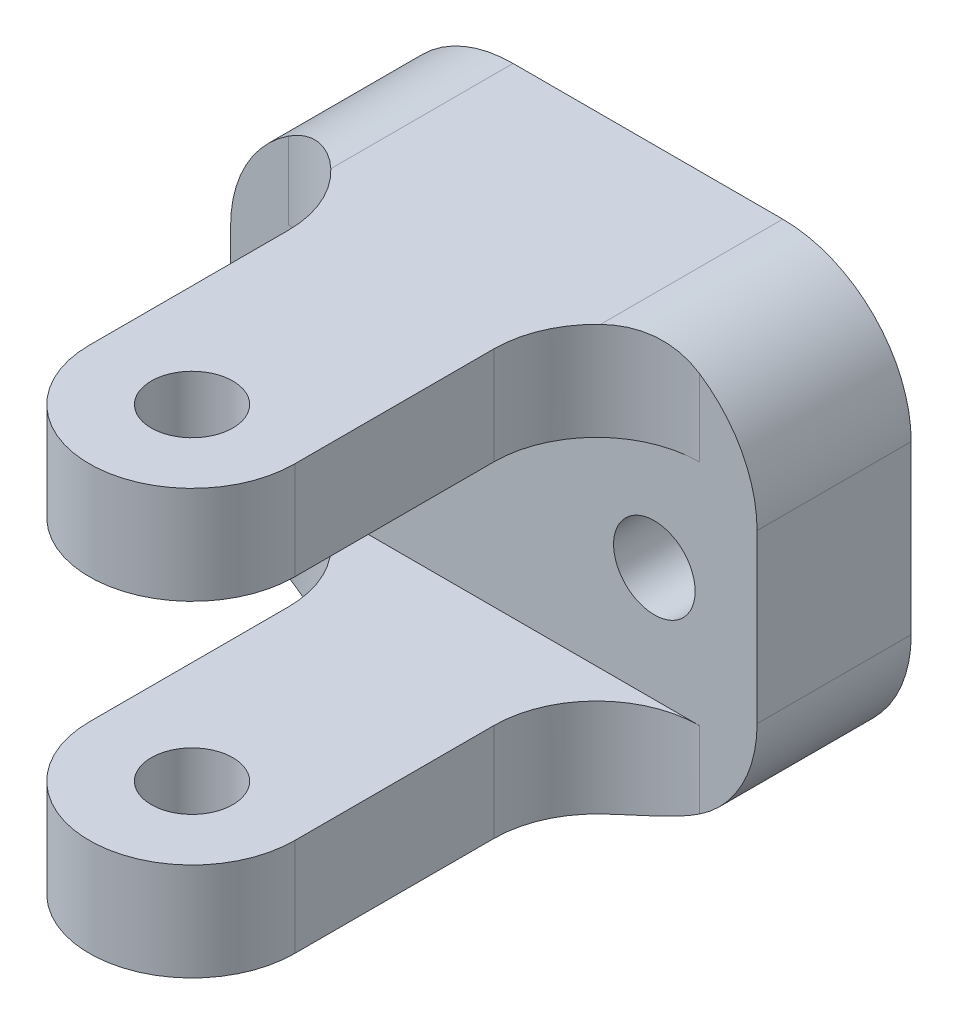
SolidWorks part; units mm, degrees
material "7075-T6 (SN)"
ref_plane "Front Plane" through (0, 0, 0) normal (0, 0, 1) x (1, 0, 0)
ref_plane "Top Plane" through (0, 0, 0) normal (0, 1, 0) x (1, 0, 0)
ref_plane "Right Plane" through (0, 0, 0) normal (1, 0, 0) x (0, 0, -1)
sketch "Sketch1" plane through (0, 0, 0) normal (0, 0, 1) x (1, 0, 0)
  line L0 (12.5, 0) -> (-12.5, 0) construction
  line L1 (-20.5, -16.51) -> (20.5, -16.51)
  line L2 (-20.5, -16.51) -> (-20.5, 16.51)
  line L3 (-20.5, 16.51) -> (20.5, 16.51)
  line L4 (20.5, -16.51) -> (20.5, 16.51)
  line L5 (-20.5, -16.51) -> (20.5, 16.51) construction
  line L6 (-20.5, 16.51) -> (20.5, -16.51) construction
  circle A0 centre (12.5, 0) radius 3.175
  circle A1 centre (-12.5, 0) radius 3.175
  point P0 (0, 0)
  dimension "D1" = 6.35
  dimension "D2" = 25
  dimension "D3" = 8
  dimension "D4" = 16.51
extrude "Boss-Extrude1" add sketch "Sketch1" along normal blind 12
sketch "Sketch2" plane through (0, 0, 12) normal (0, 0, 1) x (1, 0, 0)
  line L0 (-12.5, 0) -> (12.5, 0) construction
  line L2 (-20.5, 8.89) -> (20.5, 8.89)
  line L3 (-20.5, 8.89) -> (-20.5, 16.51)
  line L4 (-20.5, 16.51) -> (20.5, 16.51)
  line L5 (20.5, 8.89) -> (20.5, 16.51)
  line L6 (-20.5, 8.89) -> (20.5, 16.51) construction
  line L7 (-20.5, 16.51) -> (20.5, 8.89) construction
  line L8 (-20.5, 16.51) -> (-20.5, -16.51) construction
  line L9 (20.5, -8.89) -> (20.5, -16.51)
  line L10 (-20.5, -8.89) -> (-20.5, -16.51)
  line L11 (-20.5, -16.51) -> (20.5, -8.89) construction
  line L12 (-20.5, -8.89) -> (20.5, -16.51) construction
  line L13 (-20.5, -8.89) -> (20.5, -8.89)
  line L14 (-20.5, -16.51) -> (20.5, -16.51)
  circle A0 centre (-12.5, 0) radius 3.175 construction
  circle A1 centre (12.5, 0) radius 3.175 construction
  point P6 (0, 12.7)
  point P21 (0, -12.7)
  dimension "D1" = 17.78
extrude "Boss-Extrude2" add sketch "Sketch2" along normal blind 53
sketch "Sketch3" plane through (0, 0, 0) normal (0, 1, 0) x (1, 0, 0)
  point P0 (0, -35.5)
  dimension "D1" = 35.5
ref_point "UBJ Point"
sketch "Sketch4" plane through (0, 0, 0) normal (0, 1, 0) x (1, 0, 0)
  circle A0 centre (0, -35.5) radius 3.175
  dimension "D1" = 6.35
extrude "Cut-Extrude1" cut sketch "Sketch4" against normal up to surface and the other way up to surface up to face at (0, -16.51, 32.5) other way up to face at (0, 16.51, 32.5)
sketch "Sketch5" plane through (0, 0, 0) normal (0, 1, 0) x (1, 0, 0)
  line L0 (20.5, -12) -> (8.3825, -39.2302)
  line L1 (-8.3825, -39.2302) -> (-20.5, -12)
  line L4 (20.5, 0) -> (-20.5, 0)
  line L5 (-20.5, 0) -> (-20.5, -65)
  line L6 (-20.5, -65) -> (20.5, -65)
  line L7 (20.5, -65) -> (20.5, 0)
  line L9 (-20.5, -12) -> (-20.5, -65)
  line L10 (-20.5, -65) -> (20.5, -65)
  line L11 (20.5, -65) -> (20.5, -12)
  line L12 (20.5, -12) -> (-20.5, -12)
  line L13 (20.5, -65) -> (20.5, -12)
  line L14 (-20.5, -65) -> (20.5, -65)
  line L15 (-20.5, -12) -> (-20.5, -65)
  line L17 (20.5, -65) -> (20.5, -12)
  line L18 (-20.5, -65) -> (20.5, -65)
  line L19 (-20.5, -12) -> (-20.5, -65)
  arc A0 (-8.3825, -39.2302) -> (8.3825, -39.2302) centre (0, -35.5) ccw
  circle A1 centre (0, -35.5) radius 3.175 construction
  circle A2 centre (0, -35.5) radius 3.175 construction
  dimension "D3" = 6
  dimension "D1" = 0
  dimension "D2" = 0
extrude "Cut-Extrude2" [suppressed] cut sketch "Sketch5" against normal up to surface and the other way up to surface contours A0 L1 L9 L10 L11 L0 up to face at (0, -16.51, 38.675) other way up to face at (0, 16.51, 32.325)
sketch "Sketch6" plane through (0, 0, 0) normal (0, 1, 0) x (1, 0, 0)
  line L0 (-8, -35.5) -> (-8, -20)
  line L1 (8, -35.5) -> (8, -20)
  line L2 (-16, -12) -> (-20.5, -12)
  line L4 (20.5, -12) -> (-20.5, -12)
  line L5 (-20.5, -12) -> (-20.5, -65)
  line L6 (-20.5, -65) -> (20.5, -65)
  line L7 (20.5, -65) -> (20.5, -12)
  line L8 (20.5, -12) -> (16, -12)
  line L9 (-20.5, -12) -> (-20.5, -65)
  line L10 (-20.5, -65) -> (20.5, -65)
  line L11 (20.5, -65) -> (20.5, -12)
  arc A0 (-8, -35.5) -> (8, -35.5) centre (0, -35.5) ccw
  circle A1 centre (0, -35.5) radius 3.175 construction
  arc A2 (-8, -20) -> (-16, -12) centre (-16, -20) ccw
  arc A3 (8, -20) -> (16, -12) centre (16, -20) cw
  point P15 (16.2753, -10.2526)
  point P16 (14.5945, -12)
  dimension "D2" = 8
  dimension "D3" = 8
  dimension "D1" = 0
extrude "Cut-Extrude3" cut sketch "Sketch6" against normal up to surface and the other way up to surface up to face at (0, -16.51, 38.675) other way up to face at (0, 16.51, 32.325)
fillet "Fillet1" radius 10 4 edges at (-20.5, -16.51, 6) (-20.5, 16.51, 6) (20.5, -16.51, 6) (20.5, 16.51, 6)
